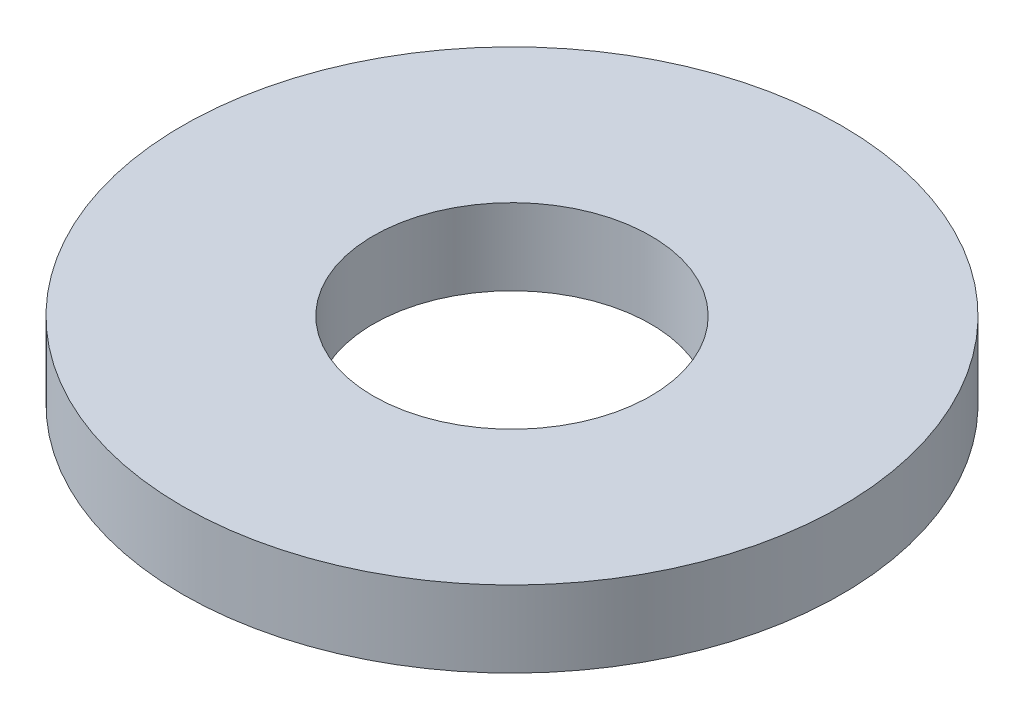
SolidWorks part; units mm, degrees
ref_plane "Front Plane" through (0, 0, 0) normal (0, 0, 1) x (1, 0, 0)
ref_plane "Top Plane" through (0, 0, 0) normal (0, 1, 0) x (1, 0, 0)
ref_plane "Right Plane" through (0, 0, 0) normal (1, 0, 0) x (0, 0, -1)
sketch "Sketch1" plane through (0, 0, 0) normal (0, 1, 0) x (1, 0, 0)
  circle A0 centre (0, 0) radius 95
  dimension "FLANGE_OD" = 190
extrude "Boss-Extrude1" add sketch "Sketch1" along normal blind 22
sketch "Sketch2" plane through (0, 0, 0) normal (0, 1, 0) x (1, 0, 0)
  circle A0 centre (0, 0) radius 40
  dimension "BORE_D" = 80
extrude "Cut-Extrude1" cut sketch "Sketch2" along normal through all
sketch "Sketch3" plane through (0, 22, 0) normal (0, 1, 0) x (1, 0, 0)
  circle A0 centre (0, 0) radius 28.0142 construction
  circle A1 centre (-28.0142, 0) radius 5.379
  dimension "BOLT_D" = 10.7581
  dimension "BOLT_PCD" = 56.0284
extrude "Cut-Extrude2" cut sketch "Sketch3" against normal blind 17.1784 rebuild error yes
pattern_circular "CirPattern1" count 6 over 360 rebuild error yes
